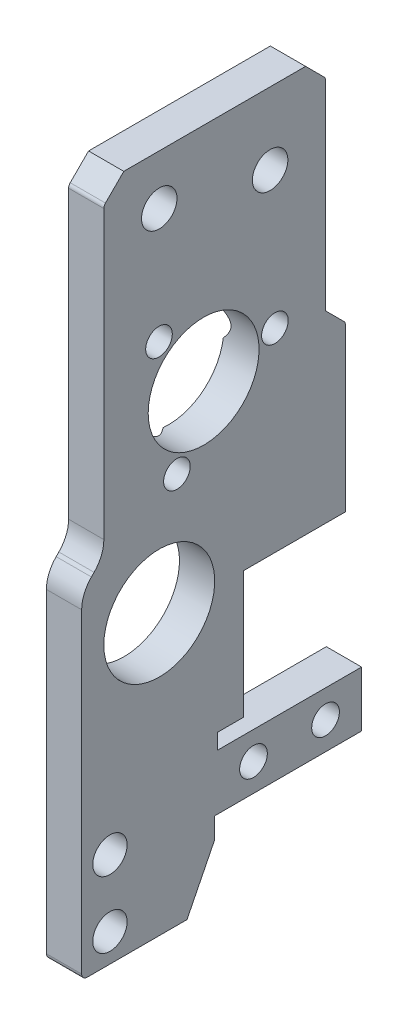
SolidWorks part; units mm, degrees
ref_plane "Front Plane" through (0, 0, 0) normal (0, 0, 1) x (1, 0, 0)
ref_plane "Top Plane" through (0, 0, 0) normal (0, 1, 0) x (1, 0, 0)
ref_plane "Right Plane" through (0, 0, 0) normal (1, 0, 0) x (0, 0, -1)
sketch "Sketch1" plane through (0, 0, 0) normal (1, 0, 0) x (0, 0, -1)
  line L2 (0, 0) -> (0, 30.2)
  line L3 (0, 30.2) -> (2, 32.2)
  line L4 (2, 32.2) -> (2, 61.31)
  line L5 (2, 61.31) -> (22, 61.31)
  line L7 (23.8, 24.71) -> (14.6, 24.71)
  line L8 (12.25, 13.26) -> (12.25, 11.86)
  line L9 (12.25, 11.86) -> (25.25, 11.86)
  line L10 (25.25, 11.86) -> (25.25, 6.86)
  line L11 (25.25, 6.86) -> (12, 6.86)
  line L12 (12, 6.86) -> (12, 0)
  line L13 (12, 0) -> (0, 0)
  line L14 (-6.9356, -4) -> (62.4069, -4) construction
  line L15 (7, 30.2) -> (0, 30.2) construction
  line L16 (7, 20.2) -> (0, 20.2) construction
  line L17 (2, 18.2) -> (2, 32.2) construction
  line L18 (12.25, 13.26) -> (14.6, 13.26)
  line L19 (14.6, 13.26) -> (14.6, 24.71)
  line L23 (22, 61.31) -> (22, 41.31)
  line L24 (22, 41.31) -> (23.8, 41.31)
  line L25 (23.8, 41.31) -> (23.8, 24.71)
  circle A0 centre (7, 25.2) radius 5
  circle A1 centre (7, 56.81) radius 1.6
  circle A2 centre (17, 54.81) radius 1.6
  circle A3 centre (22, 9.36) radius 1.25
  circle A4 centre (15.5, 9.36) radius 1.25
  circle A5 centre (2.55, 2.55) radius 1.55
  circle A6 centre (2.55, 8.55) radius 1.55
  dimension "D11" = 10
  dimension "D13" = 3.2
  dimension "D17" = 5
  dimension "D21" = 2.5
  dimension "D29" = 9.2
  dimension "D33" = 3.1
  dimension "D3" = 10.86
  dimension "D4" = 5
  dimension "D5" = 12.85
  dimension "D6" = 13
  dimension "D7" = 61.31
  dimension "D8" = 4
  dimension "D9" = 2
  dimension "D10" = 2
  dimension "D12" = 29.2
  dimension "D14" = 6.5
  dimension "D15" = 4.5
  dimension "D16" = 5
  dimension "D18" = 6.5
  dimension "D19" = 3.25
  dimension "D20" = 2.5
  dimension "D22" = 1.4
  dimension "D23" = 2.35
  dimension "D24" = 20
  dimension "D25" = 13.25
  dimension "D26" = 1.8
  dimension "D27" = 20
  dimension "D28" = 2
  dimension "D30" = 6
  dimension "D31" = 2.55
  dimension "D32" = 2.55
extrude "Boss-Extrude1" add sketch "Sketch1" along normal blind 3.18
chamfer "Chamfer1" distance 2.5 angle 63.43 1 edges at (1.59, 0, -12) first distance on face at (1.59, 0, -6)
fillet "Fillet1" [suppressed] radius 1
sketch "Sketch3" plane through (0, 0, 0) normal (-1, 0, 0) x (0, 0, 1)
  line L1 (-17.4326, 42.2448) -> (-6.9749, 46.4147) construction
  line L2 (-6.9749, 46.4147) -> (-8.5925, 35.2732) construction
  line L3 (-8.5925, 35.2732) -> (-17.4326, 42.2448) construction
  line L4 (-2, 61.31) -> (-2, 32.2) construction
  circle A0 centre (-11, 41.3109) radius 5
  circle A2 centre (-11, 41.3109) radius 6.5 construction
  circle A3 centre (-6.9749, 46.4147) radius 1.2 construction
  circle A4 centre (-8.5925, 35.2732) radius 1.2 construction
  circle A5 centre (-17.4326, 42.2448) radius 1.2 construction
  circle A6 centre (-7, 25.2) radius 5 construction
  dimension "D1" = 10
  dimension "D3" = 16.6
  dimension "D4" = 13
  dimension "D5" = 2.4
  dimension "D2" = 9
hole_wizard "CSK for M2 Flat Head Machine Screw1" positions "Sketch6" profile "Sketch7" countersink size "M2" standard "ANSI Metric"
sketch "Sketch6" plane through (0, 0, 0) normal (-1, 0, 0) x (0, 0, 1)
  point P0 (-6.9749, 46.4147)
  point P3 (-17.4326, 42.2448)
  point P6 (-8.5925, 35.2732)
sketch "Sketch7" plane through (0, 46.4147, -6.9749) normal (0, 1, 0) x (0, 0, 1)
  line L0 (0, 0) -> (0, 4.23)
  line L1 (0, 4.23) -> (1.2, 3.509)
  line L2 (1.2, 3.509) -> (1.2, 1)
  line L3 (1.2, 1) -> (2.2, 0)
  line L5 (2.2, 0) -> (0, 0)
  line L6 (-1.2, 1) -> (-2.2, 0) construction
  line L10 (0, 4.23) -> (-1.2, 3.509) construction
  line L11 (0, -6.35) -> (0, 107.95) construction
  dimension "Hole Dia." = 2.4
  dimension "Hole Depth" = 4.23
  dimension "Near C'Sink Dia." = 4.4
  dimension "Near C'Sink Angle" = 90
  dimension "Drill Angle" = 118
extrude "Cut-Extrude4" cut sketch "Sketch3" against normal through all
sketch "Sketch8" [suppressed] plane through (3.18, 0, 0) normal (1, 0, 0) x (0, 0, -1)
  line L0 (2, 61.31) -> (2, 32.2) construction
  line L1 (11, 41.3109) -> (2, 41.3109) construction
  line L2 (2, 44.3109) -> (4.1261, 44.3109)
  line L3 (4.1261, 38.3109) -> (2, 38.3109)
  line L4 (2, 38.3109) -> (2, 44.3109)
  arc A0 (4.1261, 38.3109) -> (4.1261, 44.3109) centre (11, 41.3109) ccw
  circle A1 centre (7, 25.2) radius 5 construction
  point P11 (2, 41.3109)
  dimension "D1" = 16.6
  dimension "D2" = 15
  dimension "D3" = 9
  dimension "D4" = 6
extrude "Cut-Extrude5" [suppressed] cut sketch "Sketch8" against normal through all
fillet "Fillet2" radius 3 2 edges at (1.59, 30.2, 0) (1.59, 32.2, -2)
fillet "Chamfer2" radius 1.8 3 edges at (1.59, 61.31, -22) (1.59, 61.31, -2) (1.59, 41.31, -23.8) profile chamfer
fillet "Fillet4" radius 0.5 5 edges at (1.59, 59.51, -2) (1.59, 59.51, -22) (1.59, 39.51, -23.8) (1.59, 0, 0) (1.59, 4.9989, -12)
equation "\"7.5.00mm\"=5"
